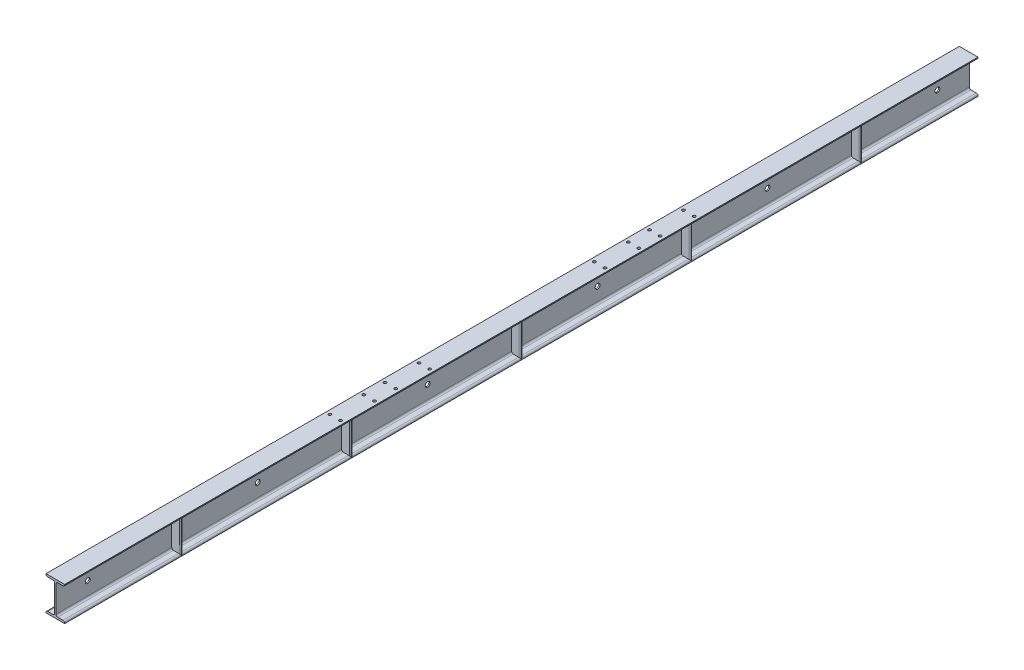
SolidWorks part; units mm, degrees
ref_plane "前视基准面" through (0, 0, 0) normal (0, 0, 1) x (1, 0, 0)
ref_plane "上视基准面" through (0, 0, 0) normal (0, 1, 0) x (1, 0, 0)
ref_plane "右视基准面" through (0, 0, 0) normal (1, 0, 0) x (0, 0, -1)
sketch "草图1" plane through (0, 0, 0) normal (0, 0, 1) x (1, 0, 0)
  line L1 (0, 0) -> (88, 0)
  line L2 (0, 0) -> (0, 160)
  line L3 (0, 160) -> (88, 160)
  line L4 (88, 0) -> (88, 160)
  dimension "D1" = 160
  dimension "D2" = 88
extrude "拉伸1" add sketch "草图1" along normal blind 4300
sketch "草图2" plane through (0, 0, 0) normal (0, 0, -1) x (-1, 0, 0)
  line L0 (-88, 0) -> (-88, 160) construction
  line L1 (-88, 150.1) -> (-47, 150.1)
  line L2 (-88, 150.1) -> (-88, 9.9)
  line L3 (-88, 9.9) -> (-47, 9.9)
  line L4 (-47, 150.1) -> (-47, 9.9)
  line L5 (0, 160) -> (0, 0) construction
  line L6 (-88, 160) -> (0, 160) construction
  line L7 (0, 150.1) -> (-41, 150.1)
  line L8 (0, 150.1) -> (0, 9.9)
  line L9 (0, 9.9) -> (-41, 9.9)
  line L10 (-41, 150.1) -> (-41, 9.9)
  line L11 (0, 0) -> (-88, 0) construction
  dimension "D1" = 9.9
  dimension "D2" = 9.9
  dimension "D3" = 6
extrude "拉伸2" cut sketch "草图2" against normal through all
fillet "圆角1" radius 8 8 edges at (41, 150.1, 2150) (47, 150.1, 2150) (41, 9.9, 2150) (47, 9.9, 2150) (88, 9.9, 2150) (0, 9.9, 2150) (0, 150.1, 2150) (88, 150.1, 2150)
sketch "草图3" plane through (41, 0, 0) normal (-1, 0, 0) x (0, 0, 1)
  line L0 (0, 80) -> (4300, 80) construction
  line L1 (0, 142.1) -> (0, 17.9) construction
  line L2 (4300, 142.1) -> (4300, 17.9) construction
  line L3 (4300, 17.9) -> (4300, 142.1) construction
  circle A0 centre (4150, 80) radius 11.5
  dimension "D2" = 23
  dimension "D1" = 150
extrude "拉伸3" cut sketch "草图3" against normal through all
pattern_linear "阵列(线性)1" count 6 spacing 800 along (0, 0, -1) of "拉伸3"
sketch "草图4" plane through (0, 0, 0) normal (-1, 0, 0) x (0, 0, 1)
  line L0 (4300, 160) -> (0, 160) construction
  line L1 (545.05, 160) -> (554.95, 160)
  line L2 (545.05, 160) -> (545.05, 0)
  line L3 (545.05, 0) -> (554.95, 0)
  line L4 (554.95, 160) -> (554.95, 0)
  line L5 (4300, 0) -> (0, 0) construction
  line L6 (150, 80) -> (545.05, 80) construction
  line L7 (950, 80) -> (554.95, 80) construction
  dimension "D1" = 9.9
extrude "拉伸4" add sketch "草图4" against normal blind 88
fillet "圆角3" radius 4.95 4 edges at (0, 80, 554.95) (0, 80, 545.05) (88, 80, 545.05) (88, 80, 554.95)
pattern_linear "阵列(线性)2" count 5 spacing 800 along (0, 0, 1) of "拉伸4", "圆角3"
sketch "草图5" plane through (0, 160, 0) normal (0, 1, 0) x (1, 0, 0)
  line L0 (44, -4300) -> (44, 0) construction
  line L1 (88, -4300) -> (0, -4300) construction
  line L2 (88, 0) -> (0, 0) construction
  line L3 (0, -1317.5) -> (88, -1317.5) construction
  line L4 (0, -4300) -> (0, 0) construction
  line L5 (88, -4300) -> (88, 0) construction
  line L6 (0, -1477.5) -> (88, -1477.5) construction
  line L7 (0, -1577.5) -> (88, -1577.5) construction
  line L8 (0, -1737.5) -> (88, -1737.5) construction
  line L9 (69, -1317.5) -> (69, -1737.5) construction
  line L10 (19, -1317.5) -> (19, -1737.5) construction
  circle A0 centre (69, -1317.5) radius 6.5
  circle A1 centre (19, -1317.5) radius 6.5
  circle A2 centre (69, -1477.5) radius 6.5
  circle A3 centre (19, -1477.5) radius 6.5
  circle A4 centre (69, -1577.5) radius 6.5
  circle A5 centre (19, -1577.5) radius 6.5
  circle A6 centre (69, -1737.5) radius 6.5
  circle A7 centre (19, -1737.5) radius 6.5
  dimension "D7" = 13
  dimension "D1" = 1317.5
  dimension "D2" = 160
  dimension "D3" = 100
  dimension "D4" = 160
  dimension "D5" = 25
  dimension "D6" = 25
extrude "拉伸5" cut sketch "草图5" against normal blind 80
pattern_linear "阵列(线性)3" count 2 spacing 1245 along (0, 0, 1) of "拉伸5"
